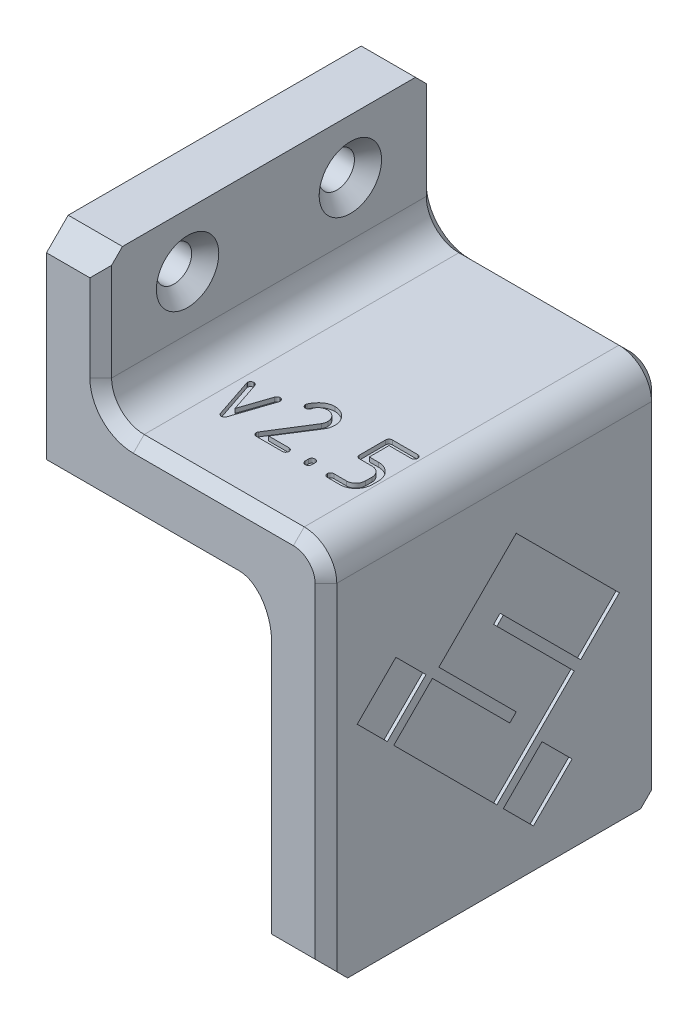
SolidWorks part; units mm, degrees
other "DetailItem1"
other "DetailItem2"
ref_plane "Front Plane" through (0, 0, 0) normal (0, 0, 1) x (1, 0, 0)
ref_plane "Top Plane" through (0, 0, 0) normal (0, 1, 0) x (1, 0, 0)
ref_plane "Right Plane" through (0, 0, 0) normal (1, 0, 0) x (0, 0, -1)
sketch "Sketch1" plane through (0, 0, 0) normal (0, 0, 1) x (1, 0, 0)
  line L0 (0, 30) -> (0, 48)
  line L1 (0, 48) -> (5, 48)
  line L2 (5, 48) -> (5, 35)
  line L3 (5, 35) -> (25.75, 35)
  line L4 (25.75, 35) -> (25.75, 0)
  line L5 (25.75, 0) -> (20.75, 0)
  line L6 (20.75, 0) -> (20.75, 30)
  line L7 (20.75, 30) -> (0, 30)
  dimension "D1" = 5
  dimension "D2" = 5
  dimension "D3" = 30
  dimension "D4" = 13
  dimension "D5" = 5
  dimension "D6" = 20.75
extrude "Boss-Extrude1" add sketch "Sketch1" along normal blind 31
sketch "Sketch2" plane through (20.75, 0, 0) normal (-1, 0, 0) x (0, 0, 1)
  line L0 (15.5, 30) -> (15.5, 0) construction
  line L1 (31, 30) -> (0, 30) construction
  line L2 (31, 0) -> (0, 0) construction
  line L5 (9.92, 2.925) -> (21.08, 21.075) construction
  circle A1 centre (21.08, 21.075) radius 0.75
  circle A2 centre (9.92, 2.925) radius 0.75
  point P0 (21.08, 21.075)
  point P3 (9.92, 2.925)
  point P4 (15.5, 15)
  dimension "D1" = 1.5
  dimension "D2" = 12.075
  dimension "D3" = 6.075
  dimension "D4" = 5.58
  dimension "D5" = 5.58
extrude "Holes - leftHand assembly" cut sketch "Sketch2" against normal blind 4.5
fillet "Fillet1" radius 3 2 edges at (5, 35, 15.5) (25.75, 35, 15.5)
sketch "Sketch3" plane through (5, 0, 0) normal (1, 0, 0) x (0, 0, -1)
  line L0 (-23, 43) -> (-8, 43) construction
  line L1 (-31, 48) -> (0, 48) construction
  line L2 (-21.08, 21.075) -> (-9.92, 2.925) construction
  circle A0 centre (-23, 43) radius 1.625
  circle A1 centre (-8, 43) radius 1.625
  point P4 (-15.5, 43)
  point P7 (-15.5, 48)
  point P12 (-15.5, 12)
  dimension "D2" = 3.25
  dimension "D1" = 15
  dimension "D3" = 31
extrude "Cut-Extrude2" cut sketch "Sketch3" against normal through all
sketch "Sketch4" plane through (0, 0, 0) normal (-1, 0, 0) x (0, 0, 1)
  line L0 (0, 30) -> (0, 27.5)
  line L1 (0, 30) -> (0, 0) construction
  line L2 (0, 30) -> (31, 30)
  line L3 (31, 30) -> (31, 27.5)
  line L4 (31, 30) -> (31, 0) construction
  line L5 (31, 30) -> (31, 0) construction
  arc A0 (0, 27.5) -> (31, 27.5) centre (15.5, -40.7624) cw
  dimension "D1" = 70
  dimension "D2" = 2.5
extrude "Boss-Extrude2" add sketch "Sketch4" against normal up to surface (20.75 mm away) up to face at (20.75, 2.925, 10.67)
chamfer "Chamfer1" distance 2 angle 45 2 edges at (10.375, 27.5, 0) (10.375, 27.5, 31) first distance on face at (10.375, 28.3688, 15.5) first distance on face at (13.375, 29.1, 31)
fillet "Fillet2" radius 3 3 edges at (20.75, 28.6766, 30.1766) (20.75, 28.546, 0.9928) (20.75, 29.2374, 15.6727)
chamfer "Chamfer2" distance 2 angle 45 4 edges at (23.25, 0, 31) (23.25, 0, 0) (2.5, 48, 0) (2.5, 48, 31)
sketch "Sketch5" plane through (25.75, 0, 0) normal (1, 0, 0) x (0, 0, -1)
  text T0 "MXET" font "DS ISO 1" height 6
extrude "MXET label" [suppressed] cut sketch "Sketch5" against normal blind 0.5
fillet "Fillet3" radius 5 4 edges at (19.4572, 27.2735, 29.5274) (19.5244, 27.3058, 1.8717) (8.875, 27.8532, 29.3532) (8.875, 27.9207, 1.9856)
chamfer "Chamfer3" distance 1.25 angle 45 2 edges at (5, 44.625, 23) (5, 44.625, 8)
sketch "Sketch9" plane through (20.75, 0, 0) normal (-1, 0, 0) x (0, 0, 1)
  line L0 (36.02, 22.95) -> (7.92, 22.95) construction
  line L1 (9.5, 22.65) -> (21.5, 22.65)
  line L2 (9.5, 22.65) -> (9.5, 23.9)
  line L3 (9.5, 23.9) -> (21.5, 23.9)
  line L4 (21.5, 22.65) -> (21.5, 23.9)
  line L5 (29, 0) -> (2, 0) construction
  line L6 (9.5, 0) -> (21.5, 0)
  line L7 (9.5, 0) -> (9.5, 1.35)
  line L8 (9.5, 1.35) -> (21.5, 1.35)
  line L9 (21.5, 0) -> (21.5, 1.35)
  line L10 (7.92, 1.05) -> (36.02, 1.05) construction
  line L11 (9.5, 23.9) -> (0, 23.9) construction
  line L12 (0, 25.6258) -> (0, 2) construction
  line L13 (21.5, 23.9) -> (31, 23.9) construction
  line L14 (31, 25.2574) -> (31, 2) construction
  dimension "D1" = 0.3
  dimension "D2" = 0.3
  dimension "D3" = 12
  dimension "D4" = 1.25
extrude "Boss-Extrude3" add sketch "Sketch9" along normal blind 1
sketch "Sketch11" plane through (0, 35, 0) normal (0, 1, 0) x (1, 0, 0)
  line L0 (8, -25) -> (22.75, -25) construction
  line L1 (8, 0) -> (8, -31) construction
  line L2 (22.75, -31) -> (22.75, 0) construction
  line L3 (22.75, -31) -> (8, -31) construction
  text T0 "v2.5" font "DS ISO 1" height 6
  dimension "D1" = 6
extrude "version" cut sketch "Sketch11" against normal blind 0.4
chamfer "Chamfer6" distance 1 angle 45 10 edges at (25.75, 17, 31) (5, 42, 31) (24.8713, 34.1213, 31) (5.8787, 35.8787, 31) (15.375, 35, 31) (25.75, 17, 0) (5, 42, 0) (24.8713, 34.1213, 0) (5.8787, 35.8787, 0) (15.375, 35, 0)
chamfer "chamfer Datums" distance 1 angle 45 4 edges at (19.75, 23.275, 9.5) (19.75, 23.275, 21.5) (19.75, 0.675, 9.5) (19.75, 0.675, 21.5)
chamfer "Chamfer8" distance 0.6 angle 45 2 edges at (20.75, 21.075, 21.83) (20.75, 2.925, 10.67)
sketch "Sketch12" plane through (25.75, 0, 0) normal (1, 0, 0) x (0, 0, -1)
  line L0 (-8.3184, 7.1356) -> (-11.8822, 3.5718)
  line L1 (-11.0903, 9.9075) -> (-8.3184, 7.1356)
  line L2 (-14.6541, 6.3437) -> (-11.0903, 9.9075)
  line L3 (-11.8822, 3.5718) -> (-14.6541, 6.3437)
  line L4 (-14.0601, 12.8773) -> (-13.4662, 13.4713)
  line L5 (-21.1878, 20.005) -> (-14.0601, 12.8773)
  line L6 (-24.7516, 16.4412) -> (-21.1878, 20.005)
  line L7 (-15.2481, 6.9377) -> (-24.7516, 16.4412)
  line L8 (-8.1204, 14.0653) -> (-15.2481, 6.9377)
  line L9 (-15.2481, 21.1929) -> (-8.1204, 14.0653)
  line L10 (-14.6541, 21.7869) -> (-15.2481, 21.1929)
  line L11 (-3.9626, 18.2231) -> (-7.5265, 14.6593)
  line L12 (-13.4662, 27.7266) -> (-3.9626, 18.2231)
  line L13 (-20.5938, 20.599) -> (-13.4662, 27.7266)
  line L14 (-13.4662, 13.4713) -> (-20.5938, 20.599)
  line L15 (-25.3456, 17.0351) -> (-28.1174, 19.807)
  line L16 (-21.7817, 20.599) -> (-25.3456, 17.0351)
  line L17 (-24.5536, 23.3708) -> (-21.7817, 20.599)
  line L18 (-28.1174, 19.807) -> (-24.5536, 23.3708)
  line L19 (-1.5198, 30.1694) -> (-29.5198, 30.1694) construction
  line L20 (-1.5198, 2.1694) -> (-1.5198, 30.1694) construction
  line L21 (-29.5198, 2.1694) -> (-1.5198, 2.1694) construction
  line L22 (-29.5198, 30.1694) -> (-29.5198, 2.1694) construction
  line L23 (-7.5265, 14.6593) -> (-14.6541, 21.7869)
extrude "Cut-Extrude3" cut sketch "Sketch12" against normal blind 0.3
